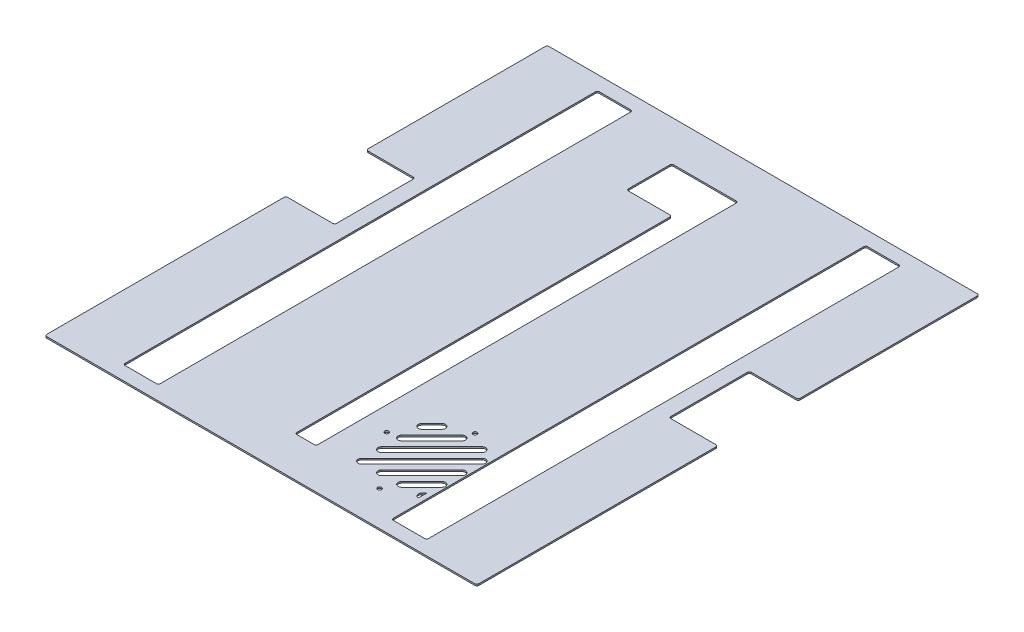
SolidWorks part; units mm, degrees
ref_plane "Front Plane" through (0, 0, 0) normal (0, 0, 1) x (1, 0, 0)
ref_plane "Top Plane" through (0, 0, 0) normal (0, 1, 0) x (1, 0, 0)
ref_plane "Right Plane" through (0, 0, 0) normal (1, 0, 0) x (0, 0, -1)
sketch "Sketch1" plane through (0, 0, 0) normal (0, 1, 0) x (1, 0, 0)
  line L1 (5911.0841, -8452.3124) -> (6341.0841, -8452.3124)
  line L2 (5911.0841, -8452.3124) -> (5911.0841, -8952.3124)
  line L3 (5911.0841, -8952.3124) -> (6341.0841, -8952.3124)
  line L4 (6341.0841, -8452.3124) -> (6341.0841, -8952.3124)
  dimension "D1" = 500
  dimension "D2" = 430
extrude "Boss-Extrude1" add sketch "Sketch1" along normal blind 1.5
sketch "Sketch2" plane through (0, 1.5, 0) normal (0, 1, 0) x (1, 0, 0)
  line L0 (5911.0841, -8452.3124) -> (5911.0841, -8952.3124) construction
  line L1 (5959.6841, -8712.448) -> (5911.0841, -8712.448)
  line L2 (5959.6841, -8712.448) -> (5959.6841, -8632.448)
  line L3 (5959.6841, -8632.448) -> (5911.0841, -8632.448)
  line L4 (5911.0841, -8712.448) -> (5911.0841, -8632.448)
  line L9 (6341.0841, -8952.3124) -> (6341.0841, -8452.3124) construction
  line L10 (6341.0841, -8712.448) -> (6292.4841, -8712.448)
  line L11 (6341.0841, -8712.448) -> (6341.0841, -8632.448)
  line L12 (6341.0841, -8632.448) -> (6292.4841, -8632.448)
  line L13 (6292.4841, -8712.448) -> (6292.4841, -8632.448)
  dimension "D1" = 48.6
  dimension "D2" = 80
  dimension "D3" = 80
  dimension "D4" = 48.6
extrude "Cut-Extrude1" cut sketch "Sketch2" against normal blind 10
sketch "Sketch3" plane through (0, 1.5, 0) normal (0, 1, 0) x (1, 0, 0)
  line L0 (5975.0841, -8541.6519) -> (5975.0841, -8938.3124)
  line L1 (6277.0841, -8938.3124) -> (6242.0841, -8938.3124)
  line L2 (6277.0841, -8938.3124) -> (6277.0841, -8466.3124)
  line L3 (6277.0841, -8466.3124) -> (6242.0841, -8466.3124)
  line L4 (6242.0841, -8938.3124) -> (6242.0841, -8466.3124)
  line L5 (5975.0841, -8466.3124) -> (6010.0841, -8466.3124)
  line L11 (5975.0841, -8938.3124) -> (6010.0841, -8938.3124)
  line L12 (6010.0841, -8466.3124) -> (6010.0841, -8938.3124)
  line L36 (5911.0841, -8712.448) -> (5911.0841, -8952.3124) construction
  line L37 (6341.0841, -8952.3124) -> (6341.0841, -8712.448) construction
  line L39 (6111.0841, -8492.3124) -> (6141.0841, -8492.3124)
  line L40 (6120.0841, -8537.3124) -> (6120.0841, -8912.3124)
  line L41 (6120.0841, -8912.3124) -> (6141.0841, -8912.3124)
  line L42 (6141.0841, -8492.3124) -> (6141.0841, -8912.3124)
  line L44 (6341.0841, -8452.3124) -> (5911.0841, -8452.3124) construction
  line L45 (5975.0841, -8466.3124) -> (5975.0841, -8541.6519)
  line L47 (5911.0841, -8952.3124) -> (6341.0841, -8952.3124) construction
  line L48 (6111.0841, -8492.3124) -> (6075.0841, -8492.3124)
  line L50 (6120.0841, -8537.3124) -> (6075.0841, -8537.3124)
  line L51 (6075.0841, -8492.3124) -> (6075.0841, -8537.3124)
  point P32 (6126.0841, -8452.3124)
  point P33 (6126.0841, -8492.3124)
  dimension "D15" = 40
  dimension "D22" = 45
  dimension "D1" = 35
  dimension "D2" = 472
  dimension "D3" = 35
  dimension "D4" = 472
  dimension "D6" = 64
  dimension "D7" = 45
  dimension "D8" = 64
  dimension "D10" = 420
  dimension "D11" = 110
  dimension "D20" = 14
  dimension "D21" = 14
extrude "Cut-Extrude2" cut sketch "Sketch3" against normal blind 10
sketch "Sketch4" plane through (0, 1.5, 0) normal (0, 1, 0) x (1, 0, 0)
  line L0 (6237.0841, -8848.0965) -> (6237.0841, -8858.0965) construction
  line L1 (6237.0841, -8898.0965) -> (6207.0841, -8898.0965) construction
  line L3 (6237.0841, -8833.0965) -> (6192.0841, -8833.0965) construction
  line L4 (6177.0841, -8898.0965) -> (6177.0841, -8848.0965) construction
  line L5 (5911.0841, -8952.3124) -> (6341.0841, -8952.3124) construction
  line L6 (6177.0841, -8898.0965) -> (6234.5841, -8840.5965)
  line L7 (6179.5841, -8885.5965) -> (6229.5841, -8835.5965)
  line L8 (6174.5841, -8880.5965) -> (6222.0841, -8833.0965)
  line L9 (6177.0841, -8898.0965) -> (6174.5841, -8900.5965)
  line L10 (6174.5841, -8880.5965) -> (6222.0841, -8833.0965)
  line L11 (6179.5841, -8865.5965) -> (6209.5841, -8835.5965)
  line L12 (6177.0841, -8898.0965) -> (6174.5841, -8900.5965) construction
  line L13 (6179.5841, -8865.5965) -> (6209.5841, -8835.5965)
  line L14 (6174.5841, -8860.5965) -> (6204.5841, -8830.5965)
  line L15 (6237.0841, -8888.0965) -> (6239.5841, -8885.5965)
  line L16 (6174.5841, -8860.5965) -> (6204.5841, -8830.5965)
  line L17 (6179.5841, -8845.5965) -> (6189.5841, -8835.5965)
  line L18 (6174.5841, -8840.5965) -> (6184.5841, -8830.5965)
  line L19 (6179.5841, -8885.5965) -> (6229.5841, -8835.5965)
  line L20 (6177.0841, -8878.0965) -> (6222.0841, -8833.0965)
  line L21 (6179.5841, -8865.5965) -> (6209.5841, -8835.5965)
  line L22 (6187.0841, -8898.0965) -> (6237.0841, -8848.0965)
  line L23 (6197.0841, -8898.0965) -> (6234.5841, -8860.5965)
  line L24 (6207.0841, -8898.0965) -> (6237.0841, -8868.0965)
  line L25 (6194.5841, -8900.5965) -> (6234.5841, -8860.5965)
  line L26 (6199.5841, -8905.5965) -> (6237.0841, -8868.0965)
  line L27 (6214.5841, -8900.5965) -> (6234.5841, -8880.5965)
  line L28 (6199.5841, -8905.5965) -> (6237.0841, -8868.0965)
  line L29 (6214.5841, -8900.5965) -> (6234.5841, -8880.5965)
  line L30 (6219.5841, -8905.5965) -> (6237.0841, -8888.0965)
  line L31 (6214.5841, -8900.5965) -> (6234.5841, -8880.5965)
  line L32 (6219.5841, -8905.5965) -> (6237.0841, -8888.0965)
  line L33 (6234.5841, -8900.5965) -> (6237.0841, -8898.0965)
  line L34 (6179.5841, -8905.5965) -> (6237.0841, -8848.0965)
  line L35 (6194.5841, -8900.5965) -> (6234.5841, -8860.5965)
  line L36 (6199.5841, -8905.5965) -> (6237.0841, -8868.0965)
  line L37 (6182.0841, -8833.0965) -> (6192.0841, -8833.0965) construction
  line L38 (6182.0841, -8833.0965) -> (6177.0841, -8833.0965) construction
  line L39 (6177.0841, -8863.0965) -> (6237.0841, -8863.0965) construction
  line L40 (6177.0841, -8838.0965) -> (6177.0841, -8833.0965) construction
  line L41 (6177.0841, -8838.0965) -> (6177.0841, -8848.0965) construction
  line L42 (6197.0841, -8898.0965) -> (6177.0841, -8898.0965) construction
  line L43 (6179.5841, -8865.5965) -> (6209.5841, -8835.5965)
  line L44 (6174.5841, -8860.5965) -> (6204.5841, -8830.5965)
  line L45 (6179.5841, -8845.5965) -> (6189.5841, -8835.5965)
  line L46 (6147.0841, -8878.0965) -> (6157.0841, -8868.0965) [skipped]
  line L47 (6147.0841, -8898.0965) -> (6157.0841, -8888.0965) [skipped]
  line L48 (6147.0841, -8888.0965) -> (6157.0841, -8878.0965) [skipped]
  line L49 (6237.0841, -8868.0965) -> (6239.5841, -8865.5965)
  line L52 (6222.0841, -8833.0965) -> (6224.5841, -8830.5965)
  line L54 (6237.0841, -8833.0965) -> (6237.0841, -8839.561) construction
  line L55 (6237.0841, -8898.0965) -> (6237.0841, -8906.6321)
  line L57 (6237.0841, -8888.0965) -> (6237.0841, -8898.0965) construction
  line L59 (6237.0841, -8848.0965) -> (6239.5841, -8845.5965)
  line L60 (6237.0841, -8868.0965) -> (6237.0841, -8879.561) construction
  arc A1 (6189.5841, -8835.5965) -> (6184.5841, -8830.5965) centre (6187.0841, -8833.0965) ccw
  arc A2 (6209.5841, -8835.5965) -> (6204.5841, -8830.5965) centre (6207.0841, -8833.0965) ccw
  arc A3 (6229.5841, -8835.5965) -> (6224.5841, -8830.5965) centre (6227.0841, -8833.0965) ccw
  arc A5 (6174.5841, -8840.5965) -> (6179.5841, -8845.5965) centre (6177.0841, -8843.0965) ccw
  arc A6 (6174.5841, -8860.5965) -> (6179.5841, -8865.5965) centre (6177.0841, -8863.0965) ccw
  arc A7 (6174.5841, -8880.5965) -> (6179.5841, -8885.5965) centre (6177.0841, -8883.0965) ccw
  arc A8 (6174.5841, -8900.5965) -> (6179.5841, -8905.5965) centre (6177.0841, -8903.0965) ccw
  arc A9 (6194.5841, -8900.5965) -> (6199.5841, -8905.5965) centre (6197.0841, -8903.0965) ccw
  arc A10 (6214.5841, -8900.5965) -> (6219.5841, -8905.5965) centre (6217.0841, -8903.0965) ccw
  arc A11 (6234.5841, -8900.5965) -> (6237.0841, -8906.6321) centre (6237.0841, -8903.0965) ccw
  arc A12 (6249.5841, -8835.5965) -> (6244.5841, -8830.5965) centre (6247.0841, -8833.0965) ccw [skipped]
  arc A13 (6239.5841, -8845.5965) -> (6234.5841, -8840.5965) centre (6237.0841, -8843.0965) ccw
  arc A14 (6239.5841, -8865.5965) -> (6234.5841, -8860.5965) centre (6237.0841, -8863.0965) ccw
  arc A15 (6239.5841, -8885.5965) -> (6234.5841, -8880.5965) centre (6237.0841, -8883.0965) ccw
  line M5 (6242.0841, -8938.3124) -> (6242.0841, -8466.3124)
  dimension "D8" = 4
  dimension "D1" = 65
  dimension "D3" = 54.2159
  dimension "D4" = 4
  dimension "D5" = 4
  dimension "D6" = 4
  dimension "D7" = 4
  dimension "D9" = 4
  dimension "D10" = 4
extrude "Cut-Extrude3" cut sketch "Sketch4" against normal blind 10 contours L27 A10 L30 M5 | L25 A9 L26 L24 L23 M5 | L8 A7 L7 A3 L52 L10 | L14 A6 L11 A2 | L18 A5 L17 A1 | L33 A11 M5 | L59 A13 L6 L9 A8 L34 region at (6202.0841, 1.5, 8858.0965) region at (6192.0841, 1.5, 8848.0965) region at (6227.0841, 1.5, 8893.0965) region at (6182.0841, 1.5, 8838.0965) region at (6217.0841, 1.5, 8883.0965) region at (6235.6369, 1.5, 8902.8482)
fillet "Fillet2" radius 2 12 edges at (6292.4841, 0.75, 8632.448) (6341.0841, 0.75, 8632.448) (6341.0841, 0.75, 8712.448) (6292.4841, 0.75, 8712.448) (5959.6841, 0.75, 8632.448) (5959.6841, 0.75, 8712.448) (5911.0841, 0.75, 8712.448) (5911.0841, 0.75, 8632.448) (5911.0841, 0.75, 8452.3124) (6341.0841, 0.75, 8452.3124) (6341.0841, 0.75, 8952.3124) (5911.0841, 0.75, 8952.3124)
fillet "Fillet3" radius 2 14 edges at (6010.0841, 0.75, 8938.3124) (5975.0841, 0.75, 8938.3124) (6010.0841, 0.75, 8466.3124) (5975.0841, 0.75, 8466.3124) (6277.0841, 0.75, 8938.3124) (6242.0841, 0.75, 8938.3124) (6277.0841, 0.75, 8466.3124) (6242.0841, 0.75, 8466.3124) (6141.0841, 0.75, 8912.3124) (6120.0841, 0.75, 8912.3124) (6141.0841, 0.75, 8492.3124) (6120.0841, 0.75, 8537.3124) (6075.0841, 0.75, 8492.3124) (6075.0841, 0.75, 8537.3124)
sketch "Sketch6" plane through (0, 1.5, 0) normal (0, 1, 0) x (1, 0, 0)
  line L0 (6177.0841, -8833.0965) -> (6242.0841, -8833.0965) construction
  line L1 (6242.0841, -8468.3124) -> (6242.0841, -8936.3124) construction
  line L2 (6242.0841, -8833.0965) -> (6242.0841, -8898.0738) construction
  line L3 (6242.0841, -8898.0738) -> (6177.0841, -8898.0965) construction
  line L4 (6177.0841, -8898.0965) -> (6177.0841, -8833.0965) construction
  line L5 (6177.0841, -8865.5965) -> (6242.0841, -8865.5852) construction
  line L6 (6209.5841, -8833.0965) -> (6209.5841, -8898.0852) construction
  line L7 (6209.5841, -8833.0965) -> (6209.5841, -8822.5908) construction
  line L8 (6177.0841, -8865.5965) -> (6164.5841, -8865.5965) construction
  line L9 (6209.5841, -8898.0852) -> (6209.5841, -8917.5908) construction
  line L10 (6237.0841, -8833.0965) -> (6237.0841, -8839.561) construction
  circle A0 centre (6209.5841, -8822.5908) radius 2
  circle A1 centre (6209.5841, -8917.5908) radius 2
  circle A2 centre (6164.5841, -8865.5965) radius 2
  dimension "D1" = 4
  dimension "D2" = 4
  dimension "D3" = 4
  dimension "D4" = 95
  dimension "D5" = 43
  dimension "D6" = 45
  dimension "D7" = 27.5
extrude "Cut-Extrude4" cut sketch "Sketch6" against normal blind 10
